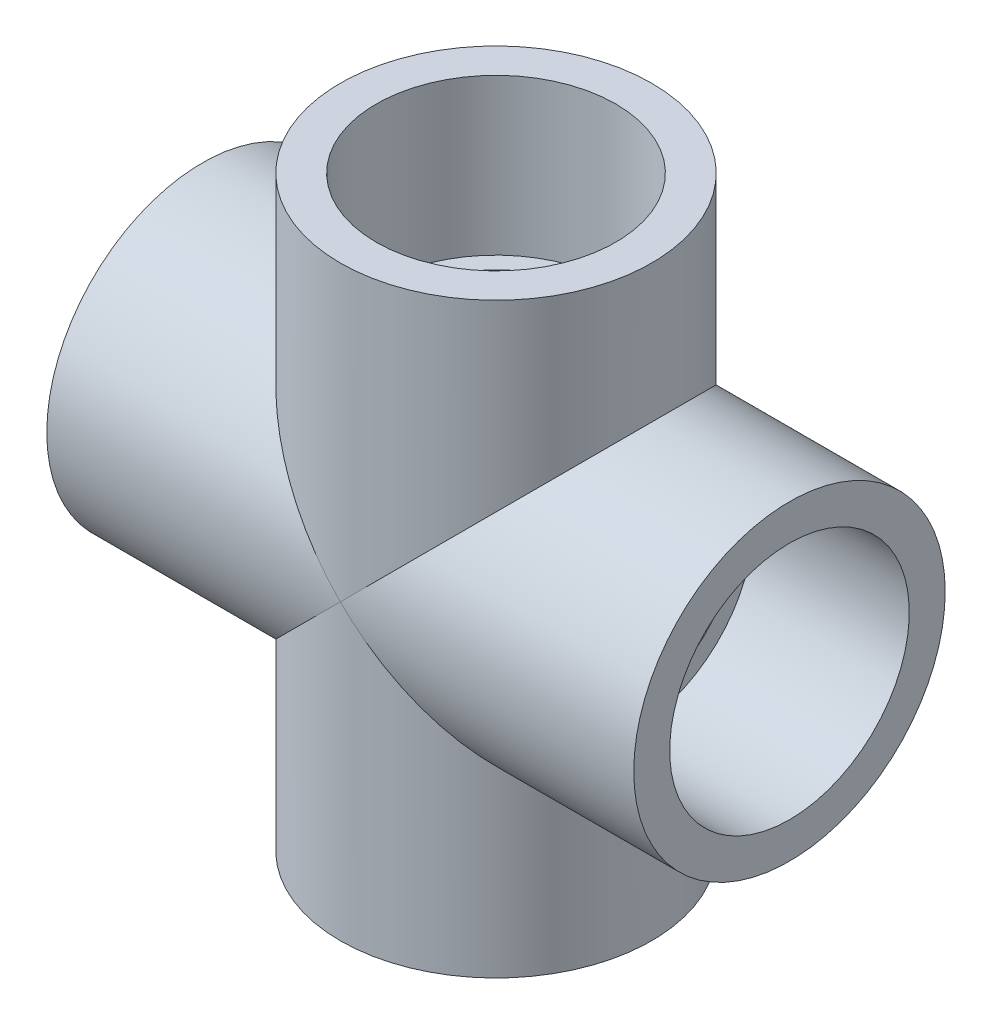
SolidWorks part; units mm, degrees
ref_plane "Front" through (0, 0, 0) normal (0, 0, 1) x (1, 0, 0)
ref_plane "Top" through (0, 0, 0) normal (0, 1, 0) x (1, 0, 0)
ref_plane "Right" through (0, 0, 0) normal (1, 0, 0) x (0, 0, -1)
sketch "Sketch1" plane through (0, 0, 0) normal (0, 1, 0) x (1, 0, 0)
  circle A0 centre (0, 0) radius 26
  dimension "Outer diameter" = 52
extrude "Boss-Extrude1" add sketch "Sketch1" along normal mid plane 98
ref_axis "Axis1" through (0, 0, 50) along (0, 0, -1)
pattern_circular "CirPattern1" count 2 every 90 about axis through (0, 0, 50) along (0, 0, -1) of "Boss-Extrude1"
sketch "Sketch2" plane through (0, 49, 0) normal (0, 1, 0) x (1, 0, 0)
  circle A1 centre (0, 0) radius 20
  dimension "Inner diameter" = 40
extrude "Cut-Extrude1" cut sketch "Sketch2" against normal blind 26
pattern_circular "CirPattern2" count 4 over 360 about axis through (0, 0, 50) along (0, 0, -1) of "Cut-Extrude1"
sketch "Sketch3" plane through (0, 23, 0) normal (0, 1, 0) x (1, 0, 0)
  circle A3 centre (0, 0) radius 17
  circle A4 centre (0, 0) radius 17
  dimension "Border" = 3
extrude "Cut-Extrude2" cut sketch "Sketch3" against normal through all contours A4
pattern_circular "CirPattern3" count 2 every 90 about axis through (0, 0, 50) along (0, 0, -1) of "Cut-Extrude2"
sketch "Sketch4" plane through (0, 0, 0) normal (0, 0, 1) x (1, 0, 0)
  line L0 (23, -17) -> (23, 17) construction
  line L1 (-23, 17) -> (-23, -17) construction
  line L2 (17, 23) -> (-17, 23) construction
  line L3 (-17, -23) -> (17, -23) construction
  line L4 (23, -17) -> (23, 17) construction
  line L5 (-23, 17) -> (-23, -17) construction
  line L6 (17, 23) -> (-17, 23) construction
  line L7 (-17, -23) -> (17, -23) construction
  line L8 (-23, 0) -> (23, 0) construction
  line L9 (0, 23) -> (0, -23) construction
  point P12 (0, 0)
other "CPoint1" parameters "Diameter"=40, "StubLength"=0
ref_axis "Axis2" through (33, 0, 0) along (-1, 0, 0)
other "CPoint2" parameters "Diameter"=40, "StubLength"=0
ref_axis "Axis3" through (-33, 0, 0) along (1, 0, 0)
other "CPoint3" parameters "Diameter"=40, "StubLength"=0
ref_axis "Axis4" through (0, 33, 0) along (0, -1, 0)
other "CPoint4" parameters "Diameter"=40, "StubLength"=0
ref_axis "Axis5" through (0, -33, 0) along (0, 1, 0)
other "RPoint1"
scale "Scale1" scale about centroid uniform scaling yes scale factor 0.2
scale "Scale2" scale about centroid uniform scaling yes scale factor 0.25
